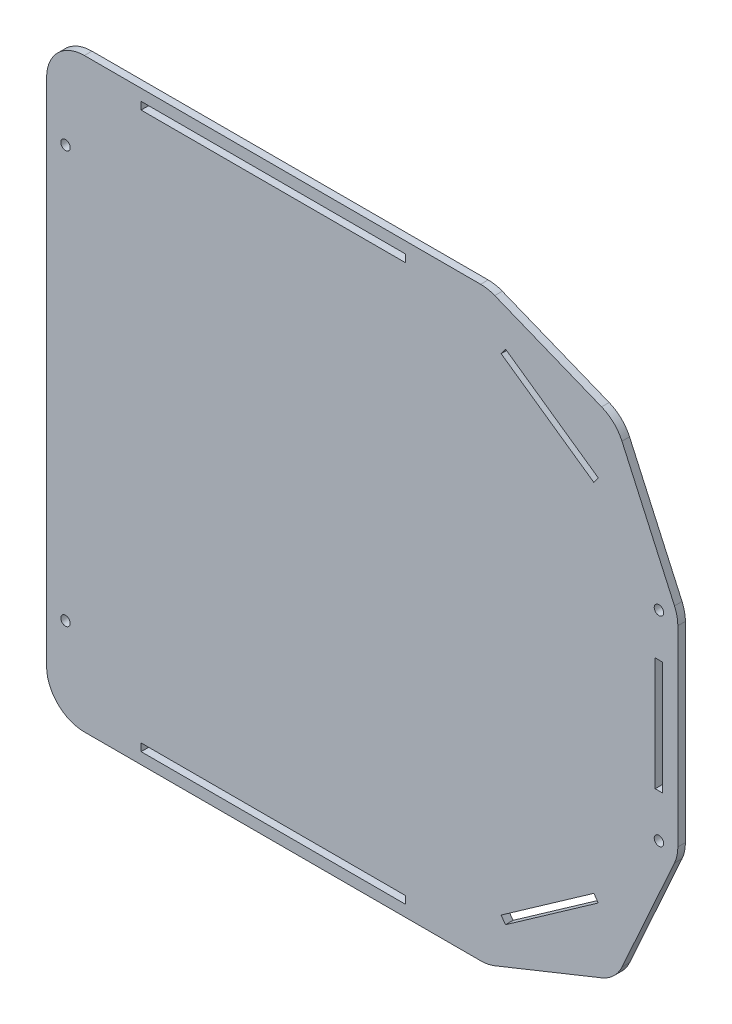
SolidWorks part; units mm, degrees
material "PVC rigido"
ref_plane "Piano frontale" through (0, 0, 0) normal (0, 0, 1) x (1, 0, 0)
ref_plane "Piano superiore" through (0, 0, 0) normal (0, 1, 0) x (1, 0, 0)
ref_plane "Piano destro" through (0, 0, 0) normal (1, 0, 0) x (0, 0, -1)
sketch "Schizzo1" plane through (0, 0, 0) normal (0, 0, 1) x (1, 0, 0)
  line L0 (25.7647, -77.5) -> (59.5674, -63.9093)
  line L1 (-91, -77.5) -> (25.7647, -77.5)
  line L2 (-91, -77.5) -> (-91, 77.5)
  line L3 (-91, 77.5) -> (25.7647, 77.5)
  line L4 (76, -27.5) -> (76, 27.5)
  line L5 (69.2392, 67.1366) -> (85.1147, 31.9616) construction
  line L6 (59.5674, -63.9093) -> (59.5674, 63.9093) construction
  line L7 (59.5674, -63.9093) -> (76, -27.5)
  line L8 (25.7647, 77.5) -> (59.5674, 63.9093)
  line L9 (59.5674, 63.9093) -> (76, 27.5)
  line L10 (25.7647, 77.5) -> (76, 77.5) construction
  line L11 (76, 77.5) -> (76, 27.5) construction
  line L12 (25.7647, -77.5) -> (76, -77.5) construction
  line L13 (76, -77.5) -> (76, -27.5) construction
  line L14 (63.8549, -72.3011) -> (27.8474, -86.7782) construction
  line L15 (85.1147, -31.9616) -> (69.2392, -67.1366) construction
  line L16 (27.8474, 86.7782) -> (63.8549, 72.3011) construction
  line L17 (0, 0) -> (25.7647, 77.5) construction
  line L18 (0, 0) -> (25.7647, -77.5) construction
  line L19 (25.7647, -77.5) -> (25.7647, 77.5) construction
  line L20 (-91, -77.5) -> (0, 0) construction
  line L21 (0, 0) -> (-91, 77.5) construction
  line L22 (0, 0) -> (-91, 0) construction
  line L23 (0, 0) -> (0, 77.5) construction
  line L24 (86, 27.8479) -> (86, -27.8479) construction
  point P0 (0, 0)
  dimension "D1" = 155
  dimension "D2" = 91
  dimension "D3" = 55
  dimension "D4" = 10
extrude "Estrusione-Estrusione1" add sketch "Schizzo1" along normal blind 2
hole_wizard "Foro filettato M3x0.5-1" positions "Schizzo3" profile "Schizzo2" tap size "M3x0.5" standard "Ansi Metric" end condition through all
sketch "Schizzo3" plane through (0, 0, 0) normal (0, 0, -1) x (-1, 0, 0)
  line L0 (86, -77.5) -> (86, -54.5) construction
  line L1 (91, -77.5) -> (-25.7647, -77.5) construction
  line L2 (86, -54.5) -> (86, 54.5) construction
  line L3 (86, 54.5) -> (86, 77.5) construction
  line L4 (-25.7647, 77.5) -> (91, 77.5) construction
  line L6 (0, 0) -> (86, 0) construction
  point P0 (86, -54.5)
  point P2 (86, 54.5)
sketch "Schizzo2" plane through (-86, -54.5, 0) normal (1, 0, 0) x (0, 1, 0)
  line L0 (0, 0) -> (0, 2)
  line L1 (0, 2) -> (1.25, 2)
  line L2 (1.25, 2) -> (1.25, 0)
  line L5 (1.25, 0) -> (0, 0)
  line L11 (0, -6.35) -> (0, 107.95) construction
  dimension "Thru Tap Drill Dia." = 2.5
  dimension "Thru Tap Drill Depth" = 2
cosmetic thread "Filettatura del foro1" parameters "D2"=3
cosmetic thread "Filettatura del foro2" parameters "D2"=3
sketch "Schizzo4" plane through (0, 0, 0) normal (0, 0, -1) x (-1, 0, 0)
  line L0 (31, -72.5) -> (31, 72.5) construction
  line L1 (66, -74.5) -> (-4, -74.5)
  line L2 (66, -74.5) -> (66, -72.5)
  line L3 (66, -72.5) -> (-4, -72.5)
  line L4 (-4, -74.5) -> (-4, -72.5)
  line L5 (66, 72.5) -> (-4, 72.5)
  line L6 (66, 72.5) -> (66, 74.5)
  line L7 (66, 74.5) -> (-4, 74.5)
  line L8 (-4, 72.5) -> (-4, 74.5)
  line L9 (31, 0) -> (91, 0) construction
  line L10 (91, 77.5) -> (91, -77.5) construction
  line L11 (91, -77.5) -> (-25.7647, -77.5) construction
  dimension "D1" = 2
  dimension "D2" = 3
  dimension "D3" = 70
  dimension "D4" = 60
extrude "Taglio-Estrusione1" cut sketch "Schizzo4" against normal blind 10
hole_wizard "Foro filettato M3x0.5-2" positions "Schizzo6" profile "Schizzo5" tap size "M3x0.5" standard "Ansi Metric" end condition through all
sketch "Schizzo6" plane through (0, 0, 2) normal (0, 0, 1) x (1, 0, 0)
  line L16 (55.0101, -61.8525) -> (71, -26.4239)
  line L17 (71, -26.4239) -> (71, 26.4239)
  line L18 (71, 26.4239) -> (55.0101, 61.8525)
  line L19 (55.0101, -61.8525) -> (71, -26.4239) construction
  line L20 (71, -26.4239) -> (71, 26.4239) construction
  line L21 (71, 26.4239) -> (55.0101, 61.8525) construction
  point P0 (71, 26.4239)
  point P2 (71, -26.4239)
  dimension "D1" = 5
sketch "Schizzo5" plane through (71, 26.4239, 2) normal (1, 0, 0) x (0, -1, 0)
  line L0 (0, 0) -> (0, 2)
  line L1 (0, 2) -> (1.25, 2)
  line L2 (1.25, 2) -> (1.25, 0)
  line L5 (1.25, 0) -> (0, 0)
  line L11 (0, -6.35) -> (0, 107.95) construction
  dimension "Thru Tap Drill Dia." = 2.5
  dimension "Thru Tap Drill Depth" = 2
cosmetic thread "Filettatura del foro3" parameters "D2"=3
cosmetic thread "Filettatura del foro4" parameters "D2"=3
sketch "Schizzo7" plane through (0, 0, 2) normal (0, 0, 1) x (1, 0, 0)
  line L0 (30.4008, 65.9495) -> (54.9474, 48.7024)
  line L1 (53.7976, 47.0659) -> (29.251, 64.3131)
  line L2 (29.251, 64.3131) -> (30.4008, 65.9495)
  line L3 (53.7976, 47.0659) -> (54.9474, 48.7024)
  line L4 (71, 26.4239) -> (4, 73.5) construction
  line L5 (4, 74.5) -> (4, 72.5) construction
  line L6 (4, 74.5) -> (4, 72.5) construction
  line L7 (29.8259, 65.1313) -> (54.3725, 47.8842) construction
  line L8 (42.0992, 56.5077) -> (37.5, 49.962) construction
  line L9 (71, 26.4239) -> (71, 15) construction
  line L10 (71, 15) -> (71, -15) construction
  line L11 (71, -15) -> (71, -26.4239) construction
  line L12 (71, -26.4239) -> (4, -73.5) construction
  line L15 (4, -72.5) -> (4, -74.5) construction
  line L16 (53.7976, -47.0659) -> (29.251, -64.3131)
  line L17 (29.251, -64.3131) -> (30.4008, -65.9495)
  line L18 (30.4008, -65.9495) -> (54.9474, -48.7024)
  line L19 (54.9474, -48.7024) -> (53.7976, -47.0659)
  line L20 (54.3725, -47.8842) -> (29.8259, -65.1313) construction
  line L21 (37.5, -49.962) -> (42.0992, -56.5077) construction
  line L23 (72, -15) -> (70, -15)
  line L24 (72, -15) -> (72, 15)
  line L25 (72, 15) -> (70, 15)
  line L26 (70, -15) -> (70, 15)
  dimension "D1" = 30
  dimension "D2" = 8
  dimension "D3" = 30
extrude "Taglio-Estrusione2" cut sketch "Schizzo7" against normal blind 10
fillet "Raccordo1" radius 10 2 edges at (-91, 77.5, 1) (-91, -77.5, 1)
fillet "Raccordo2" radius 10 6 edges at (25.7647, -77.5, 1) (59.5674, -63.9093, 1) (76, -27.5, 1) (76, 27.5, 1) (59.5674, 63.9093, 1) (25.7647, 77.5, 1)
